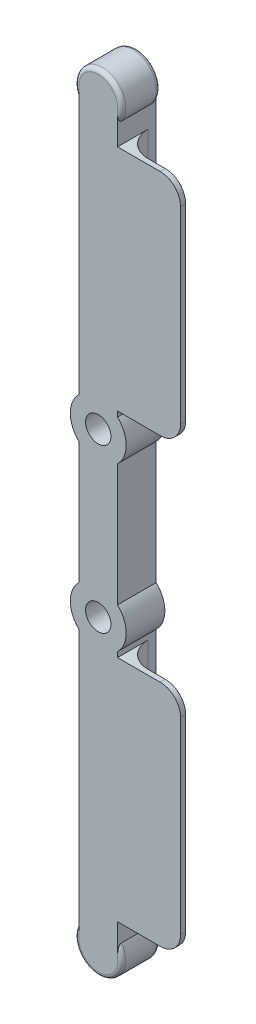
SolidWorks part; units mm, degrees
ref_plane "Front Plane" through (0, 0, 0) normal (0, 0, 1) x (1, 0, 0)
ref_plane "Top Plane" through (0, 0, 0) normal (0, 1, 0) x (1, 0, 0)
ref_plane "Right Plane" through (0, 0, 0) normal (1, 0, 0) x (0, 0, -1)
sketch "Sketch1" plane through (0, 0, 0) normal (0, 0, 1) x (1, 0, 0)
  line L0 (0, 0) -> (0, 44.9793) construction
  line L5 (3.8, 0) -> (-3.8, 0)
  line L6 (-3.8, 0) -> (-3.8, 6)
  line L7 (-3.8, 6) -> (-9.3, 6)
  line L8 (-9.3, 6) -> (-9.3, 9.28)
  line L9 (-9.3, 9.28) -> (-4.8, 13.8308)
  line L10 (-4.8, 13.8308) -> (4.8, 13.8308)
  line L11 (0, 13.8308) -> (0, 0) construction
  line L12 (9.3, 9.28) -> (4.8, 13.8308)
  line L13 (9.3, 6) -> (9.3, 9.28)
  line L14 (3.8, 6) -> (9.3, 6)
  line L15 (3.8, 0) -> (3.8, 6)
  line L17 (3.8, 0) -> (-3.8, 0)
  line L18 (3.8, 0) -> (3.8, -64)
  line L19 (3.8, -64) -> (-3.8, -64)
  line L20 (-3.8, 0) -> (-3.8, -64)
  line L21 (3.8, 0) -> (-3.8, -64) construction
  line L22 (3.8, -64) -> (-3.8, 0) construction
  circle A0 centre (0, 8.6308) radius 4.6218
  circle A1 centre (0, -48) radius 2.5
  arc A2 (3.8, -44.0238) -> (3.8, -51.9762) centre (0, -48) cw
  arc A3 (-3.8, -44.0238) -> (-3.8, -51.9762) centre (0, -48) ccw
  point P21 (0, -32)
  point P25 (3.8, -53.9708)
  dimension "D7" = 5.2
  dimension "D9" = 5
  dimension "D11" = 5.5
  dimension "D1" = 3.8
  dimension "D2" = 6
  dimension "D3" = 5.5
  dimension "D4" = 3.28
  dimension "D5" = 6.4
  dimension "D6" = 4.8
  dimension "D8" = 70
  dimension "D10" = 16
extrude "Boss-Extrude1" add sketch "Sketch1" along normal blind 7.6 contours A0 | A0 L6 L5 L15 | L5 L20 L19 L18 | A2 L18 | L20 A3 region at (0, -31.3269, 0) region at (0, 2.336, 0) region at (0, 8.6308, 0) region at (4.4899, -48, 0) region at (-4.4899, -48, 0)
ref_plane "Plane1" through (0, -64, 0) normal (0, -1, 0) x (-1, 0, 0)
sketch "Sketch4" plane through (0, 0, 7.6) normal (0, 0, 1) x (1, 0, 0)
  line L0 (0, 0) -> (0, -67.9118) construction
  line L1 (-3.8, -44.0238) -> (-3.8, 6) construction
  line L6 (-3.8, -43) -> (16.2, -43)
  line L7 (-3.8, -43) -> (-3.8, 2)
  line L8 (-3.8, 2) -> (16.2, 2)
  line L9 (16.2, -43) -> (16.2, 2)
  line L10 (-3.8, -43) -> (16.2, 2) construction
  line L11 (-3.8, 2) -> (16.2, -43) construction
  point P9 (6.2, -20.5)
  dimension "D1" = 20
  dimension "D2" = 45
  dimension "D3" = 2
extrude "Boss-Extrude2" add sketch "Sketch4" against normal blind 1
fillet "Fillet3" radius 0.8 2 edges at (0, 13.2526, 0) (0, 13.2526, 7.6)
fillet "Fillet2" radius 4 2 edges at (16.2, 2, 7.1) (16.2, -43, 7.1)
fillet "Fillet1" radius 5 1 edges at (3.8, -20.5, 6.6)
mirror "Mirror1" about plane through (0, -64, 0) normal (0, -1, 0) of "Fillet3", "Boss-Extrude2", "Fillet1", "Boss-Extrude1", "Fillet2"
